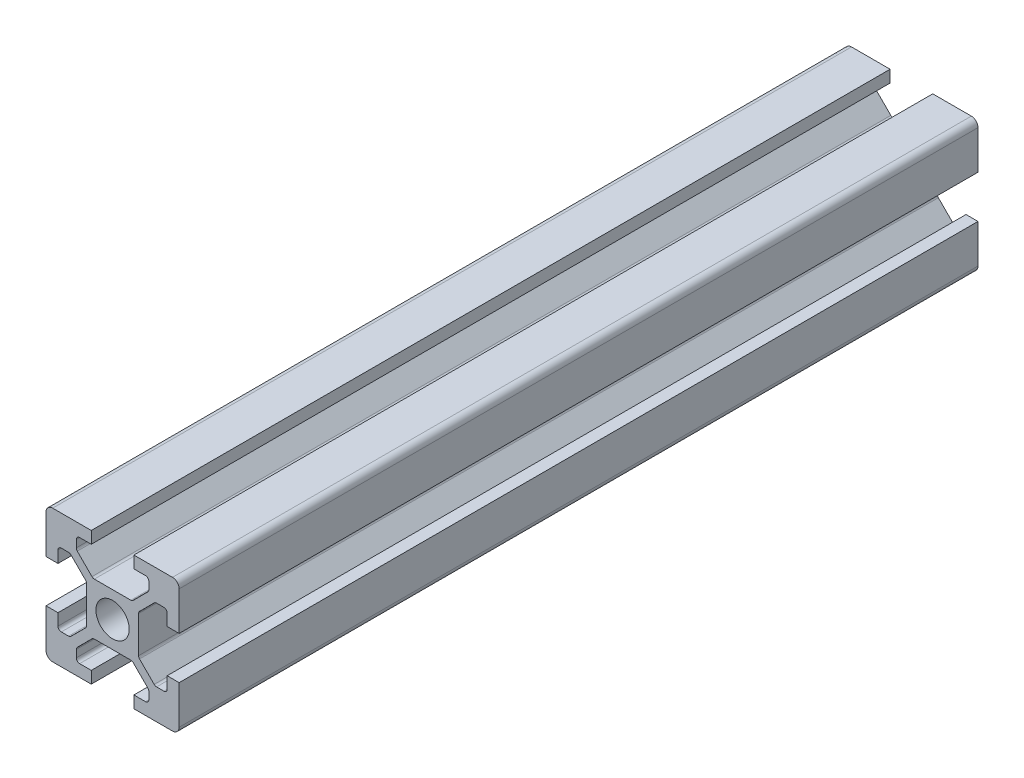
SolidWorks part; units mm, degrees
material "1060 Alloy"
ref_plane "Front Plane" through (0, 0, 0) normal (0, 0, 1) x (1, 0, 0)
ref_plane "Top Plane" through (0, 0, 0) normal (0, 1, 0) x (1, 0, 0)
ref_plane "Right Plane" through (0, 0, 0) normal (1, 0, 0) x (0, 0, -1)
sketch "Sketch1" plane through (0, 0, 0) normal (0, 0, 1) x (1, 0, 0)
  line L0 (20, 0) -> (-8.059, 28.059) construction
  line L1 (0, 0) -> (6.8, 0)
  line L2 (0, 0) -> (0, 6.8)
  line L3 (0, 20) -> (6.8, 20)
  line L4 (20, 0) -> (20, 6.8)
  line L5 (6.8, 20) -> (6.8, 18.2)
  line L6 (20, 20) -> (8.2322, 8.2322) construction
  line L7 (12.95, 6.1) -> (7.05, 6.1)
  line L8 (13.9, 7.05) -> (13.9, 12.95)
  line L9 (12.95, 13.9) -> (7.05, 13.9)
  line L10 (6.1, 7.05) -> (6.1, 12.95)
  line L11 (13.9, 6.1) -> (6.1, 13.9) construction
  line L12 (13.9, 13.9) -> (6.1, 6.1) construction
  line L13 (4.55, 16.4) -> (7.05, 13.9)
  line L14 (13.2, 18.2) -> (13.2, 20)
  line L15 (1.8, 6.8) -> (0, 6.8)
  line L16 (0, 13.2) -> (0, 20)
  line L17 (0, 13.2) -> (1.8, 13.2)
  line L18 (10, 10) -> (10, 13.9) construction
  line L19 (16.4, 4.55) -> (13.9, 7.05)
  line L20 (4.55, 16.4) -> (4.55, 18.2)
  line L21 (4.55, 18.2) -> (6.8, 18.2)
  line L22 (13.2, 18.2) -> (15.45, 18.2)
  line L23 (15.45, 18.2) -> (15.45, 16.4)
  line L24 (15.45, 16.4) -> (12.95, 13.9)
  line L25 (16.4, 4.55) -> (18.2, 4.55)
  line L26 (18.2, 4.55) -> (18.2, 6.8)
  line L27 (20, 6.8) -> (18.2, 6.8)
  line L28 (18.2, 13.2) -> (20, 13.2)
  line L29 (18.2, 13.2) -> (18.2, 15.45)
  line L30 (18.2, 15.45) -> (16.4, 15.45)
  line L31 (16.4, 15.45) -> (13.9, 12.95)
  line L32 (1.8, 4.55) -> (3.6, 4.55)
  line L33 (3.6, 15.45) -> (6.1, 12.95)
  line L34 (3.6, 15.45) -> (1.8, 15.45)
  line L35 (1.8, 15.45) -> (1.8, 13.2)
  line L36 (0, 13.2) -> (1.8, 13.2)
  line L37 (1.8, 6.8) -> (0, 6.8)
  line L38 (3.6, 4.55) -> (6.1, 7.05)
  line L39 (1.8, 6.8) -> (1.8, 4.55)
  line L40 (15.45, 3.6) -> (12.95, 6.1)
  line L41 (4.55, 3.6) -> (7.05, 6.1)
  line L42 (4.55, 1.8) -> (4.55, 3.6)
  line L43 (6.8, 1.8) -> (4.55, 1.8)
  line L44 (6.8, 1.8) -> (6.8, 0)
  line L45 (15.45, 3.6) -> (15.45, 1.8)
  line L46 (15.45, 1.8) -> (13.2, 1.8)
  line L47 (13.2, 0) -> (13.2, 1.8)
  line L48 (13.2, 20) -> (20, 20)
  line L49 (20, 13.2) -> (20, 20)
  line L50 (13.2, 0) -> (20, 0)
  line L51 (6.1, 6.1) -> (-5.5045, -5.5045) construction
  circle A0 centre (10, 10) radius 2.5
  point P25 (10, 16.4)
  point P39 (13.2, 19.1)
  point P46 (0.9, 6.8)
  dimension "D3" = 5
  dimension "D2" = 20
  dimension "D4" = 7.8
  dimension "D5" = 7.8
  dimension "D6" = 6.8
  dimension "D7" = 6.8
  dimension "D8" = 1.8
  dimension "D9" = 10.9
  dimension "D10" = 1.8
  dimension "D11" = 10.9
  dimension "D12" = 20
extrude "Boss-Extrude1" add sketch "Sketch1" along normal blind 120 contours L47 L50 L4 L27 L26 L25 L19 L8 L31 L30 L29 L28 L49 L48 L14 L22 L23 L24 L9 L13 L20 L21 L5 L3 L16 L17 L35 L34 L33 L10 L38 L32 L39 L15 L2 L1 L44 L43 L42 L41 L7 L40 L45 L46 A0 region at (0.2828, 3.4, 0)
fillet "Fillet1" radius 1 4 edges at (20, 20, 60) (20, 0, 60) (0, 0, 60) (0, 20, 60)
fillet "Fillet2" radius 0.5 6 edges at (4.55, 18.2, 60) (4.55, 16.4, 60) (7.05, 13.9, 60) (15.45, 18.2, 60) (15.45, 16.4, 60) (12.95, 13.9, 60)
fillet "Fillet3" radius 0.5 6 edges at (18.2, 15.45, 60) (16.4, 15.45, 60) (13.9, 12.95, 60) (18.2, 4.55, 60) (13.9, 7.05, 60) (16.4, 4.55, 60)
fillet "Fillet4" radius 0.5 6 edges at (1.8, 15.45, 60) (3.6, 15.45, 60) (6.1, 12.95, 60) (3.6, 4.55, 60) (1.8, 4.55, 60) (6.1, 7.05, 60)
fillet "Fillet5" radius 0.5 6 edges at (7.05, 6.1, 60) (4.55, 3.6, 60) (4.55, 1.8, 60) (15.45, 1.8, 60) (15.45, 3.6, 60) (12.95, 6.1, 60)
